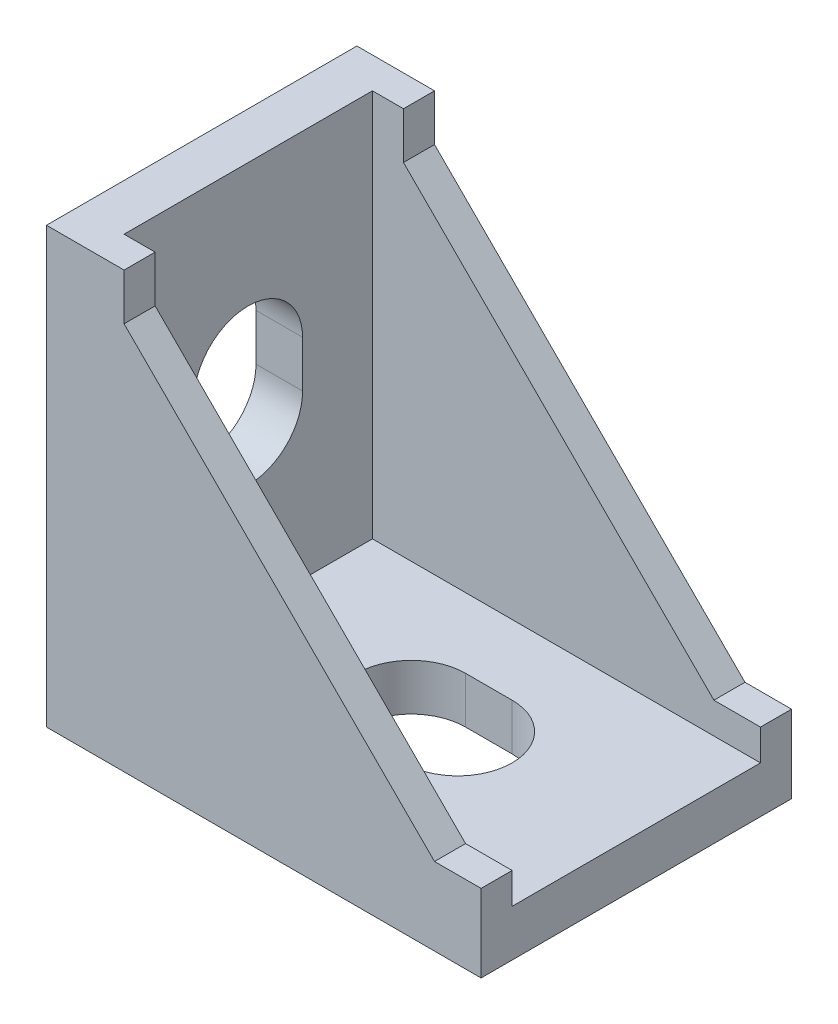
SolidWorks part; units mm, degrees
ref_plane "Front Plane" through (0, 0, 0) normal (0, 0, 1) x (1, 0, 0)
ref_plane "Top Plane" through (0, 0, 0) normal (0, 1, 0) x (1, 0, 0)
ref_plane "Right Plane" through (0, 0, 0) normal (1, 0, 0) x (0, 0, -1)
sketch "Sketch2" plane through (0, 0, 0) normal (0, 0, 1) x (1, 0, 0)
  line L0 (0, 0) -> (0, 28)
  line L1 (0, 28) -> (3, 28)
  line L2 (3, 28) -> (3, 3)
  line L3 (3, 3) -> (28, 3)
  line L4 (28, 3) -> (28, 0)
  line L5 (28, 0) -> (0, 0)
  dimension "D1" = 28
  dimension "D2" = 3
extrude "Boss-Extrude1" add sketch "Sketch2" against normal blind 20
sketch "Sketch4" plane through (0, 3, 0) normal (0, 1, 0) x (1, 0, 0)
  line L0 (0, 10) -> (28, 10) construction
  line L1 (0, 20) -> (0, 0) construction
  line L2 (28, 20) -> (28, 0) construction
  line L3 (15.5, 20) -> (15.5, 0) construction
  line L4 (28, 20) -> (3, 20) construction
  line L5 (28, 0) -> (3, 0) construction
  line L6 (13.5, 10) -> (16.5, 10) construction
  line L7 (13.5, 13.5) -> (16.5, 13.5)
  line L8 (13.5, 6.5) -> (16.5, 6.5)
  arc A0 (13.5, 13.5) -> (13.5, 6.5) centre (13.5, 10) ccw
  arc A1 (16.5, 6.5) -> (16.5, 13.5) centre (16.5, 10) ccw
  point P14 (15, 10)
  point P19 (10, 10)
  point P20 (20, 10)
  point P21 (0, 0)
  dimension "D1" = 10
  dimension "D2" = 7
  dimension "D3" = 10
extrude "Cut-Extrude1" cut sketch "Sketch4" against normal blind 10
sketch "Sketch5" plane through (3, 0, 0) normal (1, 0, 0) x (0, 0, -1)
  line L0 (10, 28) -> (10, 0) construction
  line L1 (20, 28) -> (0, 28) construction
  line L2 (20, 0) -> (0, 0) construction
  line L3 (0, 15.5) -> (20, 15.5) construction
  line L4 (0, 3) -> (0, 28) construction
  line L5 (20, 3) -> (20, 28) construction
  line L6 (10, 16.5) -> (10, 13.5) construction
  line L7 (13.5, 16.5) -> (13.5, 13.5)
  line L8 (6.5, 16.5) -> (6.5, 13.5)
  arc A0 (13.5, 16.5) -> (6.5, 16.5) centre (10, 16.5) ccw
  arc A1 (6.5, 13.5) -> (13.5, 13.5) centre (10, 13.5) ccw
  point P14 (10, 15)
  point P19 (10, 20)
  point P20 (10, 10)
  point P21 (0, 0)
  point P22 (0, 0)
  dimension "D1" = 7
  dimension "D2" = 10
  dimension "D3" = 10
extrude "Cut-Extrude2" cut sketch "Sketch5" against normal blind 10
sketch "Sketch6" plane through (0, 0, 0) normal (0, 0, 1) x (1, 0, 0)
  line L0 (3, 28) -> (5, 28)
  line L1 (5, 28) -> (5, 25)
  line L2 (5, 25) -> (25, 5)
  line L3 (25, 5) -> (28, 5)
  line L4 (28, 5) -> (28, 3)
  line L5 (3, 3) -> (3, 28) construction
  line L6 (28, 3) -> (3, 3) construction
  line L7 (3, 28) -> (3, 3)
  line L8 (3, 3) -> (28, 3)
  dimension "D1" = 2
  dimension "D2" = 2
  dimension "D3" = 135
  dimension "D4" = 20
extrude "Boss-Extrude2" add sketch "Sketch6" against normal blind 2
ref_plane "Plane1" through (0, 0, -10) normal (0, 0, -1) x (-1, 0, 0)
mirror "Mirror4" about plane through (0, 0, -10) normal (0, 0, -1) of "Boss-Extrude2"
